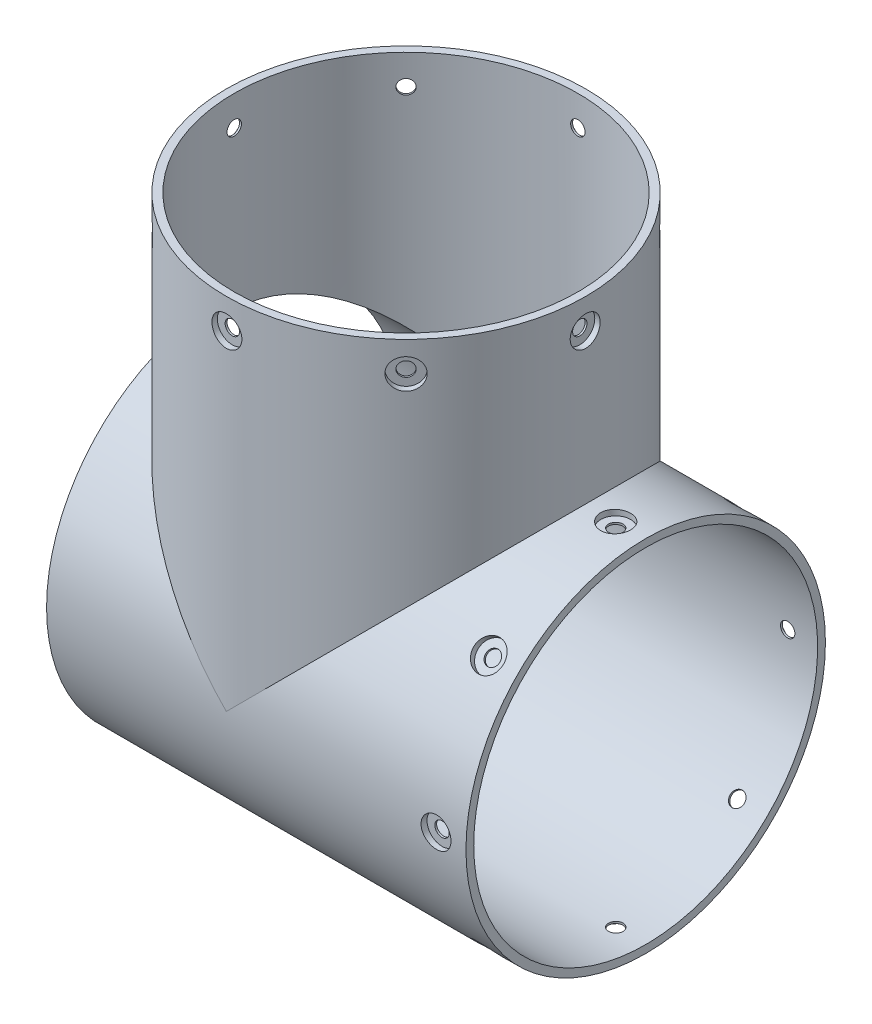
SolidWorks part; units mm, degrees
ref_plane "정면" through (0, 0, 0) normal (0, 0, 1) x (1, 0, 0)
ref_plane "윗면" through (0, 0, 0) normal (0, 1, 0) x (1, 0, 0)
ref_plane "우측면" through (0, 0, 0) normal (1, 0, 0) x (0, 0, -1)
sketch "스케치1" plane through (0, 0, 0) normal (0, 1, 0) x (1, 0, 0)
  circle A0 centre (0, 0) radius 30
  dimension "D1" = 60
extrude "보스-돌출1" add sketch "스케치1" along normal blind 60
sketch "스케치2" plane through (0, 0, 0) normal (1, 0, 0) x (0, 0, -1)
  line L0 (-30, 0) -> (30, 0) construction
  circle A0 centre (0, 0) radius 30
extrude "보스-돌출2" add sketch "스케치2" along normal blind 40 and the other way blind 30
sketch "스케치3" plane through (0, 60, 0) normal (0, 1, 0) x (1, 0, 0)
  circle A0 centre (0, 0) radius 28.7
  circle A1 centre (0, 0) radius 30 construction
  dimension "D1" = 1.3
extrude "컷-돌출1" cut sketch "스케치3" against normal blind 60
sketch "스케치4" plane through (-30, 0, 0) normal (-1, 0, 0) x (0, 0, 1)
  circle A0 centre (0, 0) radius 28.7
  circle A1 centre (0, 0) radius 30 construction
  dimension "D1" = 1.3
extrude "컷-돌출2" cut sketch "스케치4" against normal through all
ref_plane "평면1" through (0, 0, -30) normal (0, 0, -1) x (-1, 0, 0)
sketch "스케치5" plane through (0, 0, -30) normal (0, 0, -1) x (-1, 0, 0)
  line L0 (-40, 30) -> (-40, -30) construction
  point P0 (-35, 0)
  dimension "D1" = 5
hole_wizard "M2 남비 머리 나사용 카운터보어1" positions "스케치6" profile "스케치7" counterbore size "M2" standard "ISO"
sketch "스케치6" plane through (0, 0, -30) normal (0, 0, -1) x (-1, 0, 0)
  point P0 (-35, 0)
sketch "스케치7" plane through (35, 0, -30) normal (1, 0, 0) x (0, 1, 0)
  line L0 (0, 0) -> (0, 3.721)
  line L1 (0, 3.721) -> (1.2, 3)
  line L2 (1.2, 3) -> (1.2, 1)
  line L3 (1.2, 1) -> (2.5, 1)
  line L4 (2.5, 1) -> (2.5, 0)
  line L5 (2.5, 0) -> (0, 0)
  line L10 (0, 3.721) -> (-1.2, 3) construction
  line L11 (0, -6.35) -> (0, 107.95) construction
  dimension "구멍 지름" = 2.4
  dimension "구멍 깊이" = 3
  dimension "카운터보어 지름" = 5
  dimension "카운터보어 깊이" = 1
  dimension "드릴 각도" = 118
pattern_circular "원형 패턴1" count 8 over 360 about axis through (40, 0, 0) along (1, 0, 0) of "M2 남비 머리 나사용 카운터보어1"
ref_plane "평면2" through (30, 0, 0) normal (1, 0, 0) x (0, 0, -1)
sketch "스케치8" plane through (30, 0, 0) normal (1, 0, 0) x (0, 0, -1)
  line L0 (30, 60) -> (-30, 60) construction
  point P0 (0, 55)
  dimension "D1" = 5
hole_wizard "M2 남비 머리 나사용 카운터보어2" positions "스케치9" profile "스케치10" counterbore size "M2" standard "ISO"
sketch "스케치9" plane through (30, 0, 0) normal (1, 0, 0) x (0, 0, -1)
  point P0 (0, 55)
sketch "스케치10" plane through (30, 55, 0) normal (0, 1, 0) x (0, 0, -1)
  line L0 (0, 0) -> (0, 3.721)
  line L1 (0, 3.721) -> (1.2, 3)
  line L2 (1.2, 3) -> (1.2, 1)
  line L3 (1.2, 1) -> (2.5, 1)
  line L4 (2.5, 1) -> (2.5, 0)
  line L5 (2.5, 0) -> (0, 0)
  line L10 (0, 3.721) -> (-1.2, 3) construction
  line L11 (0, -6.35) -> (0, 107.95) construction
  dimension "구멍 지름" = 2.4
  dimension "구멍 깊이" = 3
  dimension "카운터보어 지름" = 5
  dimension "카운터보어 깊이" = 1
  dimension "드릴 각도" = 118
pattern_circular "원형 패턴2" count 8 over 360 about axis through (0, 60, 0) along (0, 1, 0) of "M2 남비 머리 나사용 카운터보어2"
